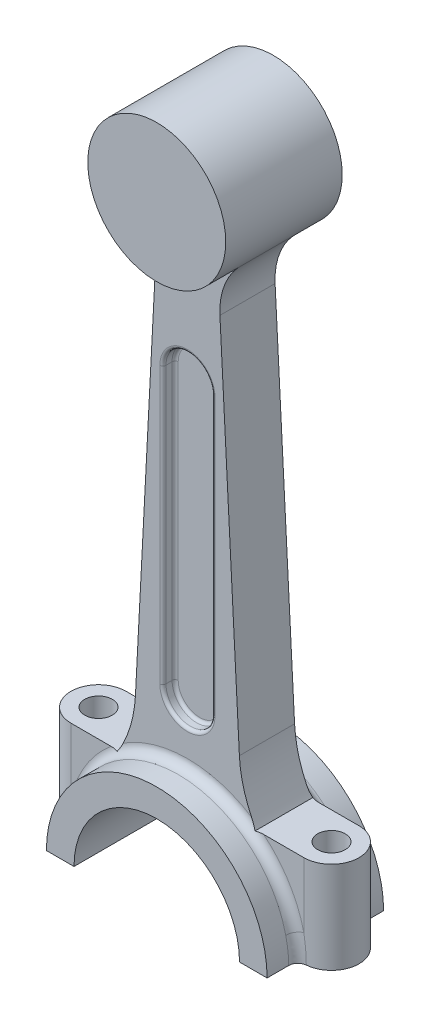
SolidWorks part; units mm, degrees
ref_plane "Front Plane" through (0, 0, 0) normal (0, 0, 1) x (1, 0, 0)
ref_plane "Top Plane" through (0, 0, 0) normal (0, 1, 0) x (1, 0, 0)
ref_plane "Right Plane" through (0, 0, 0) normal (1, 0, 0) x (0, 0, -1)
sketch "Sketch1" plane through (0, 0, 0) normal (0, 0, 1) x (1, 0, 0)
  line L0 (0, 0) -> (0, -201.2) construction
  line L1 (-10, -20.1556) -> (-17.8497, -169.9368)
  line L2 (10, -20.1556) -> (17.8497, -169.9368)
  line L3 (-36, -201.2) -> (-27, -201.2)
  line L4 (27, -201.2) -> (36, -201.2)
  circle A0 centre (0, 0) radius 22.5
  circle A1 centre (0, 0) radius 16.9
  circle A2 centre (0, -201.2) radius 27
  arc A3 (36, -201.2) -> (-36, -201.2) centre (0, -201.2) ccw
  dimension "D1" = 45
  dimension "D2" = 33.8
  dimension "D3" = 54
  dimension "D4" = 72
  dimension "D5" = 201.2
  dimension "D6" = 20
  dimension "D7" = 6
extrude "Boss-Extrude1" add sketch "Sketch1" along normal mid plane 38 contours A3 A2 | L0 A3 L3 A2 | A0 region at (20.1899, -181.0101, 0) region at (-20.1899, -181.0101, 0)
extrude "Boss-Extrude2" add sketch "Sketch1<3>" along normal mid plane 18 contours A0 L0 A3 L2 | L0 A0 L1 A3 region at (7.1843, -100.8455, 0) region at (-7.1843, -100.8455, 0)
sketch "Sketch1<3>" plane through (0, 0, 0) normal (0, 0, 1) x (1, 0, 0) same geometry as "Sketch1"
sketch "Sketch2" plane through (0, 0, 9) normal (0, 0, 1) x (1, 0, 0)
  line L0 (0, 0) -> (0, -201.2) construction
  line L1 (0, -145.6) -> (0, -55.6) construction
  line L2 (-8, -145.6) -> (-8, -55.6)
  line L3 (8, -145.6) -> (8, -55.6)
  arc A0 (-8, -145.6) -> (8, -145.6) centre (0, -145.6) ccw
  arc A1 (8, -55.6) -> (-8, -55.6) centre (0, -55.6) ccw
  point P6 (0, -100.6)
  dimension "D2" = 8
  dimension "D1" = 90
extrude "Cut-Extrude1" cut sketch "Sketch2" against normal blind 4
mirror "Mirror1" about plane through (0, 0, 0) normal (0, 0, 1) of "Cut-Extrude1"
fillet "Fillet1" radius 1 16 edges at (0, -47.6, 9) (8, -100.6, 9) (0, -153.6, 9) (0, -47.6, -9) (8, -100.6, -9) (0, -153.6, -9) (8, -100.6, -5) (0, -47.6, -5) (0, -153.6, -5) (-8, -100.6, -5) (-8, -100.6, -9) (0, -47.6, 5) (8, -100.6, 5) (0, -153.6, 5) (-8, -100.6, 5) (-8, -100.6, 9)
fillet "Fillet2" radius 40 2 edges at (17.8497, -169.9368, 0) (-17.8497, -169.9368, 0)
fillet "Fillet3" radius 22.5 2 edges at (10, -20.1556, 0) (-10, -20.1556, 0)
ref_plane "Plane1" through (0, -171.2, 0) normal (0, -1, 0) x (-1, 0, 0)
sketch "Sketch6" plane through (0, -171.2, 0) normal (0, -1, 0) x (-1, 0, 0)
  line L0 (38, 0) -> (-38, 0) construction
  line L1 (38, -9) -> (-38, -9)
  line L2 (38, 9) -> (-38, 9)
  arc A0 (38, -9) -> (38, 9) centre (38, 0) ccw
  arc A1 (-38, 9) -> (-38, -9) centre (-38, 0) ccw
  point P2 (0, 0)
  dimension "D2" = 9
  dimension "D1" = 76
extrude "Boss-Extrude3" add sketch "Sketch6" along normal up to surface (30 mm away) up to face at (31.5, -201.2, 0)
sketch "Sketch8" plane through (0, 0, -9) normal (0, 0, -1) x (-1, 0, 0)
  line L1 (-27, -201.2) -> (27, -201.2)
  line L2 (-27, -201.2) -> (27, -201.2)
  arc A1 (27, -201.2) -> (-27, -201.2) centre (0, -201.2) ccw
  arc A2 (27, -201.2) -> (-27, -201.2) centre (0, -201.2) ccw
  dimension "D1" = 0
extrude "Cut-Extrude2" cut sketch "Sketch8" against normal through all
sketch "Sketch9" plane through (0, -171.2, 0) normal (0, 1, 0) x (1, 0, 0)
  circle A0 centre (-38, 0) radius 4.5
  circle A1 centre (38, 0) radius 4.5
  dimension "D1" = 9
  dimension "D2" = 9
extrude "Cut-Extrude3" cut sketch "Sketch9" against normal through all
fillet "Fillet4" radius 3 2 edges at (0, -165.2, 9) (0, -165.2, -9)
